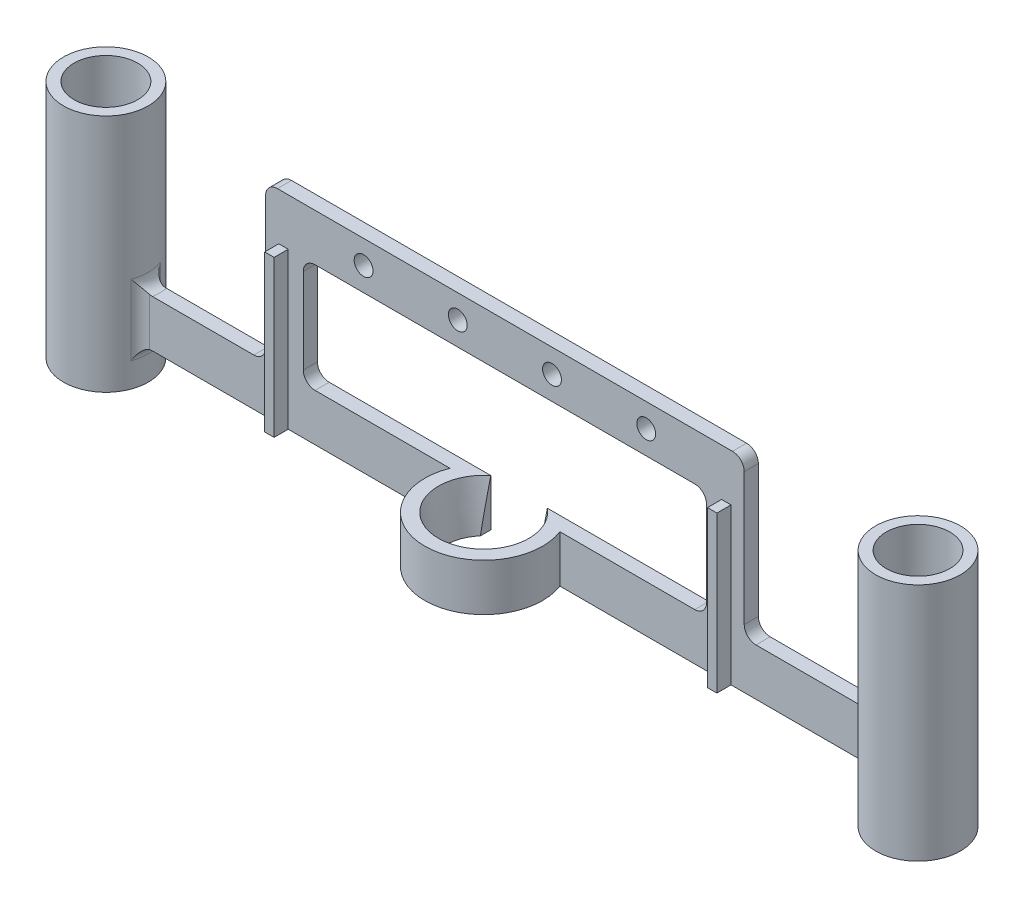
SolidWorks part; units mm, degrees
ref_plane "Front Plane" through (0, 0, 0) normal (0, 0, 1) x (1, 0, 0)
ref_plane "Top Plane" through (0, 0, 0) normal (0, 1, 0) x (1, 0, 0)
ref_plane "Right Plane" through (0, 0, 0) normal (1, 0, 0) x (0, 0, -1)
sketch "Sketch1" plane through (0, 0, 0) normal (0, 1, 0) x (1, 0, 0)
  line L0 (0, 0) -> (77.2, 0) construction
  circle A0 centre (86.2, 0) radius 9
  dimension "D2" = 18
  dimension "D1" = 77.2
extrude "Boss-Extrude1" add sketch "Sketch1" along normal blind 38.1 and the other way blind 12.7 contours A0
sketch "Sketch2" plane through (0, -12.7, 0) normal (0, -1, 0) x (-1, 0, 0)
  circle A0 centre (-86.2, 0) radius 6.75
  circle A1 centre (-86.2, 0) radius 9 construction
  dimension "D1" = 13.5
extrude "Cut-Extrude1" cut sketch "Sketch2" against normal up to surface (50.8 mm away) contours A0 up to face at (86.2, 38.1, 9)
sketch "Sketch4" plane through (0, 0, 0) normal (0, 0, 1) x (1, 0, 0)
  line L0 (77.2, 38.1) -> (77.2, -12.7) construction
  line L1 (77.5, -5) -> (0, -5)
  line L2 (77.5, -5) -> (77.5, 5)
  line L3 (77.5, 5) -> (50.8, 5)
  line L4 (0, -5) -> (0, 5)
  line L5 (77.2, 38.1) -> (77.2, -12.7) construction
  line L6 (0, 0) -> (21.2805, 0) construction
  line L7 (42.8, 5) -> (0, 5)
  line L8 (0, 38.1) -> (50.8, 38.1)
  line L9 (0, 38.1) -> (0, 28.1)
  line L10 (0, 28.1) -> (42.8, 28.1)
  line L11 (50.8, 38.1) -> (50.8, 28.1)
  line L13 (42.8, 28.1) -> (42.8, 5)
  line L15 (50.8, 28.1) -> (50.8, 5)
  dimension "D1" = 77.5
  dimension "D2" = 10
  dimension "D3" = 50.8
  dimension "D4" = 10
  dimension "D5" = 8
extrude "Boss-Extrude2" add sketch "Sketch4" along normal blind 1.5 and the other way blind 1.5 contours L7 L4 L1 L2 L3 L15 L11 L8 L9 L10 L13
mirror "Mirror2" about plane through (0, 38.1, -1.5) normal (-1, 0, 0) of bodies 103
sketch "Sketch6" plane through (0, -5, 0) normal (0, -1, 0) x (1, 0, 0)
  line L0 (0, 6) -> (0, 0) construction
  line L2 (77.3259, -1.5) -> (-77.3259, -1.5) construction
  line L4 (10, -1.5) -> (-10, -1.5)
  arc A0 (10, -1.5) -> (-10, -1.5) centre (0, 6) ccw
  dimension "D1" = 25
  dimension "D2" = 6
extrude "Boss-Extrude3" add sketch "Sketch6" against normal blind 10 contours A0 L4
sketch "Sketch7" plane through (0, 5, 0) normal (0, 1, 0) x (1, 0, 0)
  arc A0 (-11.6619, -1.5) -> (11.6619, -1.5) centre (0, -6) ccw construction
  arc A1 (-11.6619, -1.5) -> (11.6619, -1.5) centre (0, -6) ccw construction
  circle A2 centre (0, -6) radius 9.6076
sketch "Sketch8" plane through (0, -5, 0) normal (0, -1, 0) x (1, 0, 0)
  circle A0 centre (0, 6) radius 8
loft "Cut-Loft1" cut profiles "Sketch7", "Sketch8" connector at (-6.9705, 5, 12.6119) connector at (-4.2356, -5, 12.7868)
sketch "Sketch9" plane through (0, 0, -1.5) normal (0, 0, -1) x (-1, 0, 0)
  line L0 (6.0046, 5) -> (42.8, 5) construction
  line L1 (-6.0046, 5) -> (6.0046, 5)
  line L2 (-6.0046, 5) -> (-6.0046, -10.9388)
  line L3 (-6.0046, -10.9388) -> (6.0046, -10.9388)
  line L4 (6.0046, 5) -> (6.0046, -10.9388)
  line L5 (6.0046, 5) -> (42.8, 5) construction
extrude "Cut-Extrude2" cut sketch "Sketch9" against normal blind 3
sketch "Sketch10" plane through (0, 0, 1.5) normal (0, 0, 1) x (1, 0, 0)
  line L0 (0, 0) -> (0, 74.1231) construction
  line L1 (-61.5726, 33.1) -> (61.2267, 33.1) construction
  line L2 (-50.8, 38.1) -> (50.8, 38.1) construction
  line L3 (-30, 33.1) -> (-10, 33.1) construction
  circle A0 centre (-30, 33.1) radius 2
  circle A1 centre (-10, 33.1) radius 2
  circle A2 centre (10, 33.1) radius 2
  circle A3 centre (30, 33.1) radius 2
  dimension "D1" = 5
  dimension "D4" = 20
  dimension "D3" = 4
extrude "Cut-Extrude3" cut sketch "Sketch10" against normal up to surface (3 mm away) up to face at (6.7573, 9.525, -1.5)
sketch "Sketch11" plane through (0, 0, 1.5) normal (0, 0, 1) x (1, 0, 0)
  line L0 (-11.6619, -5) -> (-77.3259, -5) construction
  line L1 (-48, 28.1) -> (-46, 28.1)
  line L2 (-48, 28.1) -> (-48, -5)
  line L3 (-48, -5) -> (-46, -5)
  line L4 (-46, 28.1) -> (-46, -5)
  line L5 (77.3259, -5) -> (11.6619, -5) construction
  line L6 (46, 28.1) -> (48, 28.1)
  line L7 (46, 28.1) -> (46, -5)
  line L8 (46, -5) -> (48, -5)
  line L9 (48, 28.1) -> (48, -5)
  line L10 (0, 0) -> (0, 21.8896) construction
  dimension "D1" = 2
  dimension "D2" = 46
extrude "Boss-Extrude4" add sketch "Sketch11" along normal blind 3 contours L2 L3 L4 L1 | L7 L8 L9 L6
fillet "Fillet1" radius 2.5 16 edges at (50.8, 5, 0) (-50.8, 5, 0) (-42.8, 5, 0) (42.8, 5, 0) (42.8, 28.1, 0) (-42.8, 28.1, 0) (-77.3259, 0, 1.5) (-77.2, -5, 0) (-77.3259, 0, -1.5) (-77.2, 5, 0) (77.3259, 0, -1.5) (77.2, -5, 0) (77.3259, 0, 1.5) (77.2, 5, 0) (50.8, 38.1, 0) (-50.8, 38.1, 0)
